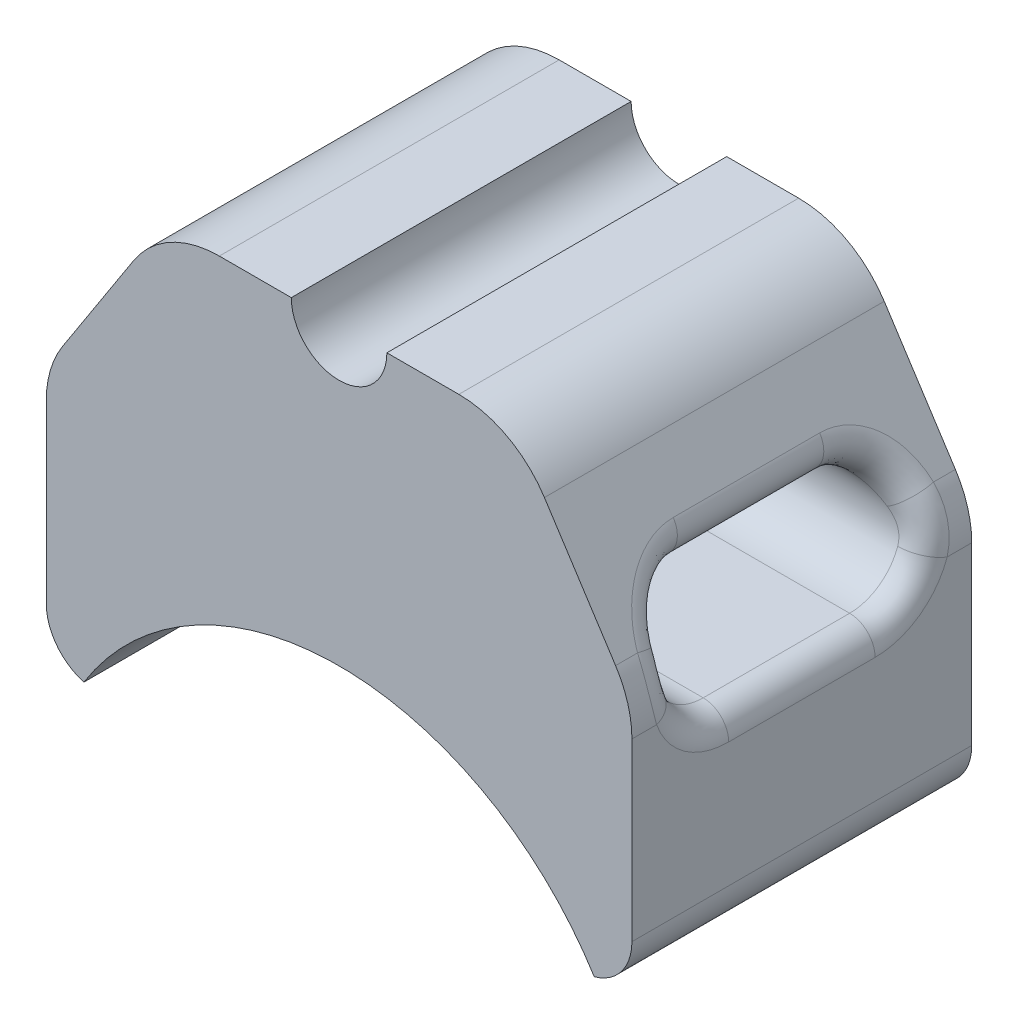
SolidWorks part; units mm, degrees
ref_plane "Front Plane" through (0, 0, 0) normal (0, 0, 1) x (1, 0, 0)
ref_plane "Top Plane" through (0, 0, 0) normal (0, 1, 0) x (1, 0, 0)
ref_plane "Right Plane" through (0, 0, 0) normal (1, 0, 0) x (0, 0, -1)
sketch "Sketch1" plane through (0, 0, 0) normal (0, 0, 1) x (1, 0, 0)
  line L0 (0, 0) -> (0, 12.7)
  line L1 (5.8618, 21.761) -> (12.2118, 21.761)
  line L5 (16.9743, 21.761) -> (23.3243, 21.761)
  line L6 (27.3079, 0) -> (29.1861, 0)
  line L7 (29.1861, 0) -> (29.1861, 12.7)
  line L8 (0, 0) -> (1.8782, 0)
  line L9 (23.3243, 21.761) -> (29.1861, 12.7)
  line L10 (5.8618, 21.761) -> (0, 12.7)
  line L11 (12.2118, 21.761) -> (16.9743, 21.761) construction
  arc A5 (12.2118, 21.761) -> (16.9743, 21.761) centre (14.5931, 21.761) ccw
  arc A7 (1.8782, 0) -> (27.3079, 0) centre (14.5931, -7.9189) cw
  dimension "D1" = 12.7
  dimension "D2" = 2.3813
  dimension "D3" = 14.9792
  dimension "D4" = 1.8782
  dimension "D5" = 6.35
  dimension "D6" = 9.061
  dimension "D7" = 7.9189
extrude "Boss-Extrude2" add sketch "Sketch1" along normal blind 16.9342 contours L6 L7 L9 L5 A5 L1 L10 L0 L8 A7
fillet "Fillet1" radius 5.08 4 edges at (0, 12.7, 8.4671) (5.8618, 21.761, 8.4671) (29.1861, 12.7, 8.4671) (23.3243, 21.761, 8.4671)
fillet "Fillet2" radius 2.54 2 edges at (0, 0, 8.4671) (29.1861, 0, 8.4671)
ref_plane "Plane1" through (31.7261, 0, 0) normal (1, 0, 0) x (0, 0, -1)
sketch "Sketch6" plane through (31.7261, 0, 0) normal (1, 0, 0) x (0, 0, -1)
  line L0 (-4.8144, 12.4701) -> (-12.1121, 12.4701) construction
  line L1 (-4.8144, 9.9301) -> (-12.1121, 9.9301)
  line L2 (-4.8144, 15.0101) -> (-12.1121, 15.0101)
  line L3 (-16.9342, 19.4404) -> (-16.9342, 13.9594) construction
  line L4 (0, 11.2001) -> (-16.9342, 11.2001) construction
  arc A0 (-4.8144, 9.9301) -> (-4.8144, 15.0101) centre (-4.8144, 12.4701) ccw
  arc A1 (-12.1121, 15.0101) -> (-12.1121, 9.9301) centre (-12.1121, 12.4701) ccw
  point P2 (-8.4633, 12.4701)
  dimension "D1" = 8.4709
  dimension "D2" = 1.27
extrude "Cut-Extrude3" cut sketch "Sketch6" against normal through all both and the other way through all
fillet "Fillet3" radius 1.27 8 edges at (27.8714, 14.7322, 3.6593) (27.8714, 14.7322, 13.2673) (27.6917, 15.0101, 8.4633) (28.9628, 12.6896, 2.2839) (29.1861, 10.2704, 3.5444) (29.1861, 9.9301, 8.4633) (29.1861, 10.2704, 13.3821) (29.0745, 12.2593, 14.6434)
fillet "Fillet4" radius 1.27 8 edges at (1.3147, 14.7322, 3.6593) (1.3147, 14.7322, 13.2673) (1.4944, 15.0101, 8.4633) (0.1117, 12.2593, 2.2832) (0, 10.2704, 3.5444) (0, 9.9301, 8.4633) (0, 10.2704, 13.3821) (0.2233, 12.6896, 14.6426)
